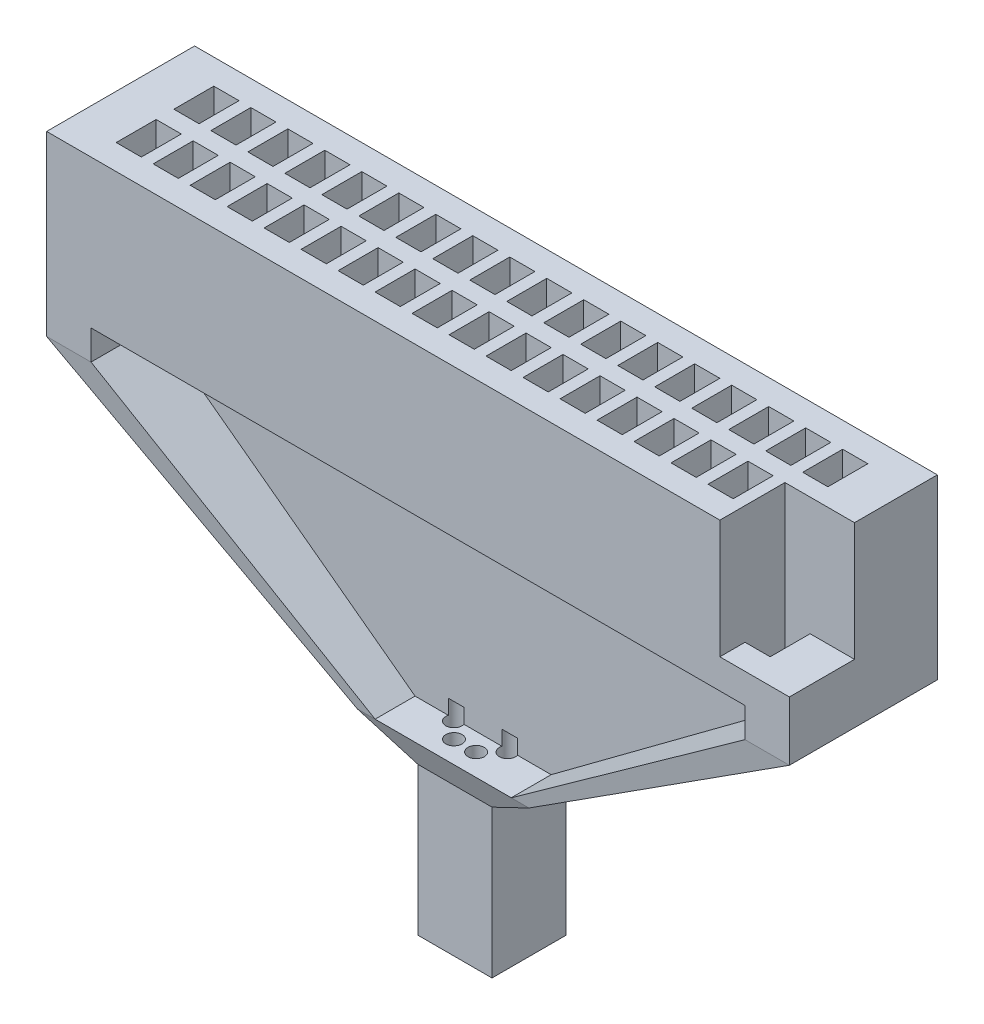
SolidWorks part; units mm, degrees
note: The reader was unsure of these and kept them because the rebuilt part matched: shared geometry of "Sketch13<3>".
ref_plane "Front Plane" through (0, 0, 0) normal (0, 0, 1) x (1, 0, 0)
ref_plane "Top Plane" through (0, 0, 0) normal (0, 1, 0) x (1, 0, 0)
ref_plane "Right Plane" through (0, 0, 0) normal (1, 0, 0) x (0, 0, -1)
sketch "main_block" plane through (0, 0, 0) normal (0, 1, 0) x (1, 0, 0)
  line L1 (-5.6188, 1.2192) -> (7.132, 1.2192)
  line L2 (-5.6188, 1.2192) -> (-5.6188, -1.3208)
  line L3 (-5.6188, -1.3208) -> (7.132, -1.3208)
  line L4 (7.132, 1.2192) -> (7.132, -1.3208)
  dimension "D1" = 12.7508
  dimension "D2" = 2.54
sketch "top_holes" plane through (0, 0, 0) normal (0, 1, 0) x (1, 0, 0)
  line L0 (7.132, 1.2192) -> (7.132, -1.3208) construction
  line L1 (6.37, 0.7874) -> (5.9382, 0.7874)
  line L2 (6.37, 0.7874) -> (6.37, 0.1016)
  line L3 (6.37, 0.1016) -> (5.9382, 0.1016)
  line L4 (5.9382, 0.7874) -> (5.9382, 0.1016)
  line L5 (-5.6188, 1.2192) -> (7.132, 1.2192) construction
  line L6 (5.3032, 0.7874) -> (5.3032, 0.1016)
  line L7 (5.735, 0.7874) -> (5.3032, 0.7874)
  line L8 (5.735, 0.7874) -> (5.735, 0.1016)
  line L9 (5.735, 0.1016) -> (5.3032, 0.1016)
  line L10 (4.6682, 0.7874) -> (4.6682, 0.1016)
  line L11 (5.1, 0.7874) -> (4.6682, 0.7874)
  line L12 (5.1, 0.7874) -> (5.1, 0.1016)
  line L13 (5.1, 0.1016) -> (4.6682, 0.1016)
  line L14 (4.0332, 0.7874) -> (4.0332, 0.1016)
  line L15 (4.465, 0.7874) -> (4.0332, 0.7874)
  line L16 (4.465, 0.7874) -> (4.465, 0.1016)
  line L17 (4.465, 0.1016) -> (4.0332, 0.1016)
  line L18 (3.3982, 0.7874) -> (3.3982, 0.1016)
  line L19 (3.83, 0.7874) -> (3.3982, 0.7874)
  line L20 (3.83, 0.7874) -> (3.83, 0.1016)
  line L21 (3.83, 0.1016) -> (3.3982, 0.1016)
  line L22 (2.7632, 0.7874) -> (2.7632, 0.1016)
  line L23 (3.195, 0.7874) -> (2.7632, 0.7874)
  line L24 (3.195, 0.7874) -> (3.195, 0.1016)
  line L25 (3.195, 0.1016) -> (2.7632, 0.1016)
  line L26 (2.1282, 0.7874) -> (2.1282, 0.1016)
  line L27 (2.56, 0.7874) -> (2.1282, 0.7874)
  line L28 (2.56, 0.7874) -> (2.56, 0.1016)
  line L29 (2.56, 0.1016) -> (2.1282, 0.1016)
  line L30 (1.4932, 0.7874) -> (1.4932, 0.1016)
  line L31 (1.925, 0.7874) -> (1.4932, 0.7874)
  line L32 (1.925, 0.7874) -> (1.925, 0.1016)
  line L33 (1.925, 0.1016) -> (1.4932, 0.1016)
  line L34 (0.8582, 0.7874) -> (0.8582, 0.1016)
  line L35 (1.29, 0.7874) -> (0.8582, 0.7874)
  line L36 (1.29, 0.7874) -> (1.29, 0.1016)
  line L37 (1.29, 0.1016) -> (0.8582, 0.1016)
  line L38 (0.2232, 0.7874) -> (0.2232, 0.1016)
  line L39 (0.655, 0.7874) -> (0.2232, 0.7874)
  line L40 (0.655, 0.7874) -> (0.655, 0.1016)
  line L41 (0.655, 0.1016) -> (0.2232, 0.1016)
  line L42 (-0.4117, 0.7874) -> (-0.4117, 0.1016)
  line L43 (0.0201, 0.7874) -> (-0.4117, 0.7874)
  line L44 (0.0201, 0.7874) -> (0.0201, 0.1016)
  line L45 (0.0201, 0.1016) -> (-0.4117, 0.1016)
  line L46 (-1.0467, 0.7874) -> (-1.0467, 0.1016)
  line L47 (-0.6149, 0.7874) -> (-1.0467, 0.7874)
  line L48 (-0.6149, 0.7874) -> (-0.6149, 0.1016)
  line L49 (-0.6149, 0.1016) -> (-1.0467, 0.1016)
  line L50 (-1.6817, 0.7874) -> (-1.6817, 0.1016)
  line L51 (-1.2499, 0.7874) -> (-1.6817, 0.7874)
  line L52 (-1.2499, 0.7874) -> (-1.2499, 0.1016)
  line L53 (-1.2499, 0.1016) -> (-1.6817, 0.1016)
  line L54 (-2.3167, 0.7874) -> (-2.3167, 0.1016)
  line L55 (-1.8849, 0.7874) -> (-2.3167, 0.7874)
  line L56 (-1.8849, 0.7874) -> (-1.8849, 0.1016)
  line L57 (-1.8849, 0.1016) -> (-2.3167, 0.1016)
  line L58 (-2.9517, 0.7874) -> (-2.9517, 0.1016)
  line L59 (-2.5199, 0.7874) -> (-2.9517, 0.7874)
  line L60 (-2.5199, 0.7874) -> (-2.5199, 0.1016)
  line L61 (-2.5199, 0.1016) -> (-2.9517, 0.1016)
  line L62 (-3.5867, 0.7874) -> (-3.5867, 0.1016)
  line L63 (-3.1549, 0.7874) -> (-3.5867, 0.7874)
  line L64 (-3.1549, 0.7874) -> (-3.1549, 0.1016)
  line L65 (-3.1549, 0.1016) -> (-3.5867, 0.1016)
  line L66 (-4.2217, 0.7874) -> (-4.2217, 0.1016)
  line L67 (-3.7899, 0.7874) -> (-4.2217, 0.7874)
  line L68 (-3.7899, 0.7874) -> (-3.7899, 0.1016)
  line L69 (-3.7899, 0.1016) -> (-4.2217, 0.1016)
  line L70 (-4.8567, 0.7874) -> (-4.8567, 0.1016)
  line L71 (-4.4249, 0.7874) -> (-4.8567, 0.7874)
  line L72 (-4.4249, 0.7874) -> (-4.4249, 0.1016)
  line L73 (-4.4249, 0.1016) -> (-4.8567, 0.1016)
  line L74 (5.3032, -0.2032) -> (5.3032, -0.889)
  line L75 (5.735, -0.2032) -> (5.3032, -0.2032)
  line L76 (5.735, -0.2032) -> (5.735, -0.889)
  line L77 (5.735, -0.889) -> (5.3032, -0.889)
  line L78 (4.6682, -0.2032) -> (4.6682, -0.889)
  line L79 (5.1, -0.2032) -> (4.6682, -0.2032)
  line L80 (5.1, -0.2032) -> (5.1, -0.889)
  line L81 (5.1, -0.889) -> (4.6682, -0.889)
  line L82 (4.0332, -0.2032) -> (4.0332, -0.889)
  line L83 (4.465, -0.2032) -> (4.0332, -0.2032)
  line L84 (4.465, -0.2032) -> (4.465, -0.889)
  line L85 (4.465, -0.889) -> (4.0332, -0.889)
  line L86 (3.3982, -0.2032) -> (3.3982, -0.889)
  line L87 (3.83, -0.2032) -> (3.3982, -0.2032)
  line L88 (3.83, -0.2032) -> (3.83, -0.889)
  line L89 (3.83, -0.889) -> (3.3982, -0.889)
  line L90 (2.7632, -0.2032) -> (2.7632, -0.889)
  line L91 (3.195, -0.2032) -> (2.7632, -0.2032)
  line L92 (3.195, -0.2032) -> (3.195, -0.889)
  line L93 (3.195, -0.889) -> (2.7632, -0.889)
  line L94 (2.1282, -0.2032) -> (2.1282, -0.889)
  line L95 (2.56, -0.2032) -> (2.1282, -0.2032)
  line L96 (2.56, -0.2032) -> (2.56, -0.889)
  line L97 (2.56, -0.889) -> (2.1282, -0.889)
  line L98 (1.4932, -0.2032) -> (1.4932, -0.889)
  line L99 (1.925, -0.2032) -> (1.4932, -0.2032)
  line L100 (1.925, -0.2032) -> (1.925, -0.889)
  line L101 (1.925, -0.889) -> (1.4932, -0.889)
  line L102 (0.8582, -0.2032) -> (0.8582, -0.889)
  line L103 (1.29, -0.2032) -> (0.8582, -0.2032)
  line L104 (1.29, -0.2032) -> (1.29, -0.889)
  line L105 (1.29, -0.889) -> (0.8582, -0.889)
  line L106 (0.2232, -0.2032) -> (0.2232, -0.889)
  line L107 (0.655, -0.2032) -> (0.2232, -0.2032)
  line L108 (0.655, -0.2032) -> (0.655, -0.889)
  line L109 (0.655, -0.889) -> (0.2232, -0.889)
  line L110 (-0.4117, -0.2032) -> (-0.4117, -0.889)
  line L111 (0.0201, -0.2032) -> (-0.4117, -0.2032)
  line L112 (0.0201, -0.2032) -> (0.0201, -0.889)
  line L113 (0.0201, -0.889) -> (-0.4117, -0.889)
  line L114 (-1.0467, -0.2032) -> (-1.0467, -0.889)
  line L115 (-0.6149, -0.2032) -> (-1.0467, -0.2032)
  line L116 (-0.6149, -0.2032) -> (-0.6149, -0.889)
  line L117 (-0.6149, -0.889) -> (-1.0467, -0.889)
  line L118 (-1.6817, -0.2032) -> (-1.6817, -0.889)
  line L119 (-1.2499, -0.2032) -> (-1.6817, -0.2032)
  line L120 (-1.2499, -0.2032) -> (-1.2499, -0.889)
  line L121 (-1.2499, -0.889) -> (-1.6817, -0.889)
  line L122 (-2.3167, -0.2032) -> (-2.3167, -0.889)
  line L123 (-1.8849, -0.2032) -> (-2.3167, -0.2032)
  line L124 (-1.8849, -0.2032) -> (-1.8849, -0.889)
  line L125 (-1.8849, -0.889) -> (-2.3167, -0.889)
  line L126 (-2.9517, -0.2032) -> (-2.9517, -0.889)
  line L127 (-2.5199, -0.2032) -> (-2.9517, -0.2032)
  line L128 (-2.5199, -0.2032) -> (-2.5199, -0.889)
  line L129 (-2.5199, -0.889) -> (-2.9517, -0.889)
  line L130 (-3.5867, -0.2032) -> (-3.5867, -0.889)
  line L131 (-3.1549, -0.2032) -> (-3.5867, -0.2032)
  line L132 (-3.1549, -0.2032) -> (-3.1549, -0.889)
  line L133 (-3.1549, -0.889) -> (-3.5867, -0.889)
  line L134 (-4.2217, -0.2032) -> (-4.2217, -0.889)
  line L135 (-3.7899, -0.2032) -> (-4.2217, -0.2032)
  line L136 (-3.7899, -0.2032) -> (-3.7899, -0.889)
  line L137 (-3.7899, -0.889) -> (-4.2217, -0.889)
  line L138 (-4.8567, -0.2032) -> (-4.8567, -0.889)
  line L139 (-4.4249, -0.2032) -> (-4.8567, -0.2032)
  line L140 (-4.4249, -0.2032) -> (-4.4249, -0.889)
  line L141 (-4.4249, -0.889) -> (-4.8567, -0.889)
  line L142 (5.9382, -0.2032) -> (5.9382, -0.889)
  line L143 (6.37, -0.2032) -> (5.9382, -0.2032)
  line L144 (6.37, -0.2032) -> (6.37, -0.889)
  line L145 (6.37, -0.889) -> (5.9382, -0.889)
  line L148 (-5.6188, 1.2192) -> (-5.6188, -1.3208) construction
  dimension "D1" = 0.4318
  dimension "D2" = 0.6858
  dimension "D3" = 0.762
  dimension "D4" = 0.4318
  dimension "D5" = 18
  dimension "D6" = 2
extrude "well_block" add sketch "main_block" against normal blind 2.54
extrude "omnetics_wells" cut sketch "top_holes" against normal blind 2.54
ref_plane "Plane1" through (0, -6.35, 0) normal (0, 1, 0) x (1, 0, 0)
sketch "Sketch4" plane through (0, -6.35, 0) normal (0, 1, 0) x (1, 0, 0)
  line L1 (1.9249, 0.889) -> (-0.4117, 0.889)
  line L2 (1.9249, 0.889) -> (1.9249, -0.889)
  line L3 (1.9249, -0.889) -> (-0.4117, -0.889)
  line L4 (-0.4117, 0.889) -> (-0.4117, -0.889)
  line L5 (1.9249, 0.889) -> (-0.4117, -0.889) construction
  line L6 (1.9249, -0.889) -> (-0.4117, 0.889) construction
  point P0 (0.7566, 0)
  dimension "D1" = 2.3367
  dimension "D2" = 1.778
sketch "Sketch5" plane through (0, -2.54, 0) normal (0, -1, 0) x (1, 0, 0)
  line L1 (-4.8567, 0.2032) -> (6.37, 0.2032)
  line L2 (-4.8567, 0.2032) -> (-4.8567, -0.1016)
  line L3 (-4.8567, -0.1016) -> (6.37, -0.1016)
  line L4 (6.37, 0.2032) -> (6.37, -0.1016)
sketch "Sketch6" plane through (0, -6.35, 0) normal (0, 1, 0) x (1, 0, 0)
  line L1 (-0.4117, 0.1016) -> (1.925, 0.1016)
  line L2 (-0.4117, 0.1016) -> (-0.4117, -0.2032)
  line L3 (-0.4117, -0.2032) -> (1.925, -0.2032)
  line L4 (1.925, 0.1016) -> (1.925, -0.2032)
sketch "Sketch7" plane through (0, -6.35, 0) normal (0, 1, 0) x (1, 0, 0)
  line L0 (-0.4117, -0.889) -> (-0.4117, 0.889)
  line L1 (-0.4117, -0.889) -> (-0.7165, -0.889)
  line L2 (-0.4117, 0.889) -> (-0.7165, 0.889)
  line L3 (-0.7165, -0.889) -> (-0.7165, 0.889)
  dimension "D1" = 0.3048
sketch "Sketch8" plane through (0, -2.54, 0) normal (0, -1, 0) x (1, 0, 0)
  line L0 (-4.8567, 1.3208) -> (-4.8567, -1.2192)
  line L1 (-4.8567, 1.3208) -> (-5.6187, 1.3208)
  line L2 (-4.8567, -1.2192) -> (-5.6187, -1.2192)
  line L3 (-5.6187, 1.3208) -> (-5.6187, -1.2192)
  line L4 (-5.6188, 1.3208) -> (7.132, 1.3208) construction
  line L5 (7.132, -1.2192) -> (-5.6188, -1.2192) construction
  dimension "D1" = 0.762
  dimension "D2" = 0
  dimension "D3" = 0
extrude "supportbeam1" add sketch "Sketch8" along normal blind 0.508
sketch "Sketch9" plane through (0, -6.35, 0) normal (0, 1, 0) x (1, 0, 0)
  line L0 (1.925, -0.889) -> (1.9249, 0.889)
  line L1 (1.925, -0.889) -> (2.2298, -0.889)
  line L2 (1.9249, 0.889) -> (2.2297, 0.889)
  line L3 (2.2298, -0.889) -> (2.2297, 0.889)
  dimension "D1" = 0.3048
sketch "Sketch10" plane through (0, -2.54, 0) normal (0, -1, 0) x (1, 0, 0)
  line L0 (6.37, -1.2192) -> (6.37, 1.3208)
  line L1 (6.37, -1.2192) -> (7.132, -1.2192)
  line L2 (6.37, 1.3208) -> (7.132, 1.3208)
  line L3 (7.132, -1.2192) -> (7.132, 1.3208)
  line L4 (-5.6188, 1.3208) -> (-5.6187, 1.3208) construction
  line L5 (7.132, -1.2192) -> (-4.8567, -1.2192) construction
  dimension "D1" = 0.762
  dimension "D2" = 0
  dimension "D3" = 0
extrude "supportbeam2" add sketch "Sketch10" along normal blind 0.508
loft "arm1" add profiles "Sketch9" section "Sketch9" section face at (6.751, -3.048, 0.0508) connector at (1.925, -6.35, 0.889) connector at (6.37, -3.048, 1.3208)
loft "arm2" add profiles "Sketch7" section "Sketch7" section face at (-5.2377, -3.048, 0.0508) connector at (-0.4117, -6.35, 0.889) connector at (-4.8567, -3.048, 1.3208)
extrude "wall_divider" add sketch "Sketch5" along normal blind 0.508
loft "wall_divider2" add profiles "Sketch6" section face at (0.7566, -3.048, 0.0508) section "Sketch6"
sketch "Sketch12" plane through (0, -6.35, 0) normal (0, 1, 0) x (1, 0, 0)
  line L1 (-0.7165, 0.889) -> (2.2299, 0.889)
  line L2 (-0.7165, 0.889) -> (-0.7165, -0.889)
  line L3 (-0.7165, -0.889) -> (2.2299, -0.889)
  line L4 (2.2299, 0.889) -> (2.2299, -0.889)
  line L6 (-0.4117, 0.889) -> (-0.7165, 0.889) construction
  line L7 (-0.7165, -0.889) -> (-0.4117, -0.889) construction
  dimension "D1" = 0
  dimension "D2" = 2.9464
  dimension "D3" = 0
ref_plane "Plane2" through (0, -6.858, 0) normal (0, 1, 0) x (1, 0, 0)
sketch "Sketch13" plane through (0, -6.858, 0) normal (0, 1, 0) x (1, 0, 0)
  line L0 (0.8582, -0.2032) -> (0.8582, -0.889) construction
  line L1 (1.3916, 0.5842) -> (0.1216, 0.5842)
  line L2 (1.3916, 0.5842) -> (1.3916, -0.6858)
  line L3 (1.3916, -0.6858) -> (0.1216, -0.6858)
  line L4 (0.1216, 0.5842) -> (0.1216, -0.6858)
  line L5 (1.3916, 0.5842) -> (0.1216, -0.6858) construction
  line L6 (1.3916, -0.6858) -> (0.1216, 0.5842) construction
  line L7 (0.655, -0.889) -> (0.655, -0.2032) construction
  line L8 (6.37, -0.2032) -> (1.925, -0.2032) construction
  line L9 (1.925, 0.1016) -> (6.37, 0.1016) construction
  point P0 (0.7566, 0)
  dimension "D1" = 1.27
  dimension "D2" = 1.27
  dimension "D3" = 0.4826
  dimension "D4" = 0.5334
  dimension "D5" = 0.5334
  dimension "D6" = 0.4826
loft "exit_base" add profiles "Sketch12", "Sketch13"
extrude "tetrode_funnel" add sketch "Sketch13<3>" against normal blind 2.54
sketch "Sketch13<3>" plane through (0, -6.858, 0) normal (0, 1, 0) x (1, 0, 0) same geometry as "Sketch13"
sketch "Sketch17" plane through (0, 0, 0) normal (0, 1, 0) x (1, 0, 0)
  line L1 (5.9382, -0.2032) -> (7.132, -0.2032)
  line L2 (5.9382, -0.2032) -> (5.9382, -1.3208)
  line L3 (5.9382, -1.3208) -> (7.132, -1.3208)
  line L4 (7.132, -0.2032) -> (7.132, -1.3208)
extrude "ground_wire_hole" cut sketch "Sketch17" against normal blind 2.032
sketch "Sketch18" plane through (0, -9.398, 0) normal (0, -1, 0) x (-1, 0, 0)
  line L0 (-0.1216, -0.6858) -> (-1.3916, -0.6858) construction
  line L1 (-1.3916, -0.6858) -> (-1.3916, 0.5842) construction
  line L2 (-1.3916, 0.5842) -> (-0.1216, 0.5842) construction
  circle A0 centre (-1.2138, -0.2413) radius 0.1397
  circle A1 centre (-1.2138, 0.1397) radius 0.1397
  circle A2 centre (-0.9444, 0.4091) radius 0.1397
  circle A3 centre (-0.5634, 0.4091) radius 0.1397
  circle A4 centre (-0.294, 0.1397) radius 0.1397
  circle A5 centre (-0.294, -0.2413) radius 0.1397
  circle A6 centre (-0.5634, -0.5107) radius 0.1397
  circle A7 centre (-0.9444, -0.5107) radius 0.1397
  point P18 (-0.7539, -0.0508)
  dimension "D1" = 8
  dimension "D2" = 0.4445
  dimension "D3" = 0.1778
  dimension "D4" = 0
  dimension "D5" = 0.381
  dimension "D6" = 0.4445
extrude "tetrodes" cut sketch "Sketch18" against normal blind 3.302
